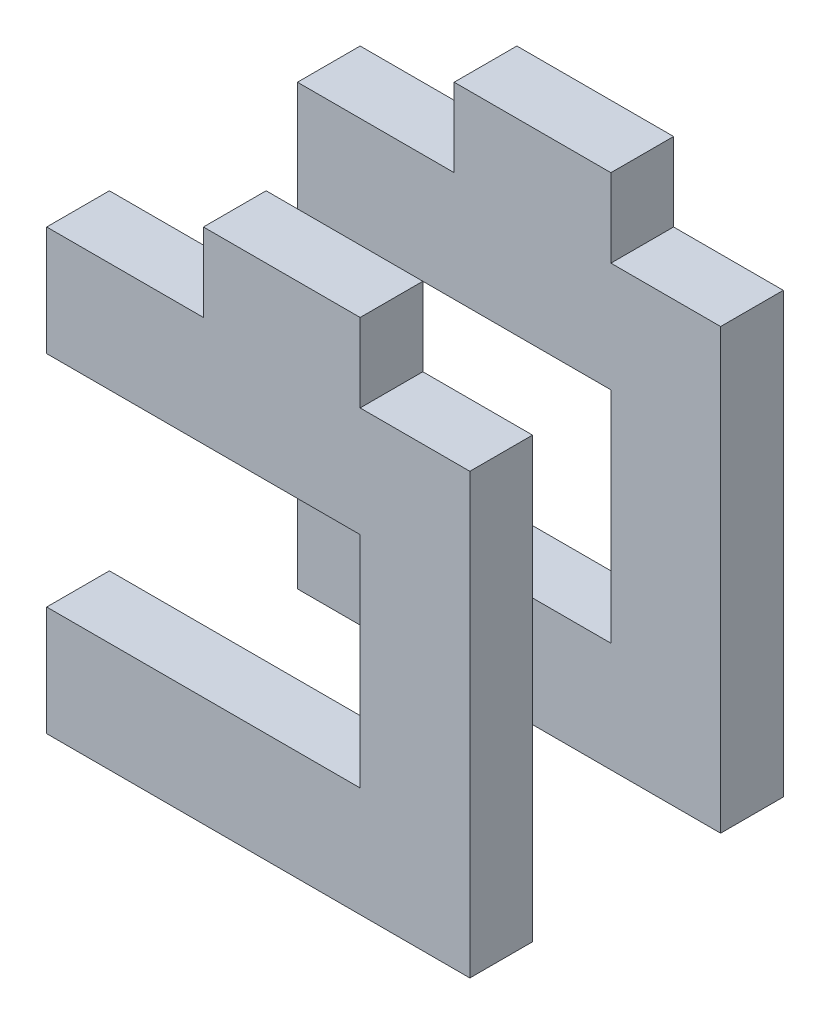
SolidWorks part; units mm, degrees
ref_plane "前视基准面" through (0, 0, 0) normal (0, 0, 1) x (1, 0, 0)
ref_plane "上视基准面" through (0, 0, 0) normal (0, 1, 0) x (1, 0, 0)
ref_plane "右视基准面" through (0, 0, 0) normal (1, 0, 0) x (0, 0, -1)
sketch "草图8" plane through (0, 0, 0) normal (0, 0, 1) x (1, 0, 0)
  line L0 (7713.407, 2376.5701) -> (7713.407, 2369.5701)
  line L1 (7713.407, 2369.5701) -> (7703.407, 2369.5701)
  line L2 (7713.407, 2376.5701) -> (7703.407, 2376.5701)
  line L3 (7703.407, 2376.5701) -> (7703.407, 2378.5701)
  line L4 (7703.407, 2369.5701) -> (7703.407, 2367.5701)
  line L5 (7716.907, 2367.5701) -> (7716.907, 2378.5701)
  line L6 (7703.407, 2367.5701) -> (7703.407, 2366.0701)
  line L7 (7703.407, 2366.0701) -> (7716.907, 2366.0701)
  line L8 (7716.907, 2367.5701) -> (7716.907, 2366.0701)
  line L9 (7703.407, 2378.5701) -> (7703.407, 2380.0701)
  line L10 (7703.407, 2380.0701) -> (7708.407, 2380.0701)
  line L11 (7716.907, 2378.5701) -> (7716.907, 2380.0701)
  line L12 (7716.907, 2380.0701) -> (7713.407, 2380.0701)
  line L13 (7713.407, 2380.0701) -> (7713.407, 2382.5701)
  line L14 (7708.407, 2380.0701) -> (7708.407, 2382.5701)
  line L15 (7708.407, 2382.5701) -> (7713.407, 2382.5701)
extrude "凸台-拉伸1" add sketch "草图8" along normal blind 2 contours L12 L13 L15 L14 L10 L9 L3 L2 L0 L1 L4 L6 L7 L8 L5 L11
ref_axis "基准轴2" through (7703.407, 2376.5701, 0) along (0, 0, 1)
pattern_linear "阵列(线性)1" count 2 spacing 8 along (0, 0, 1) of bodies 106
